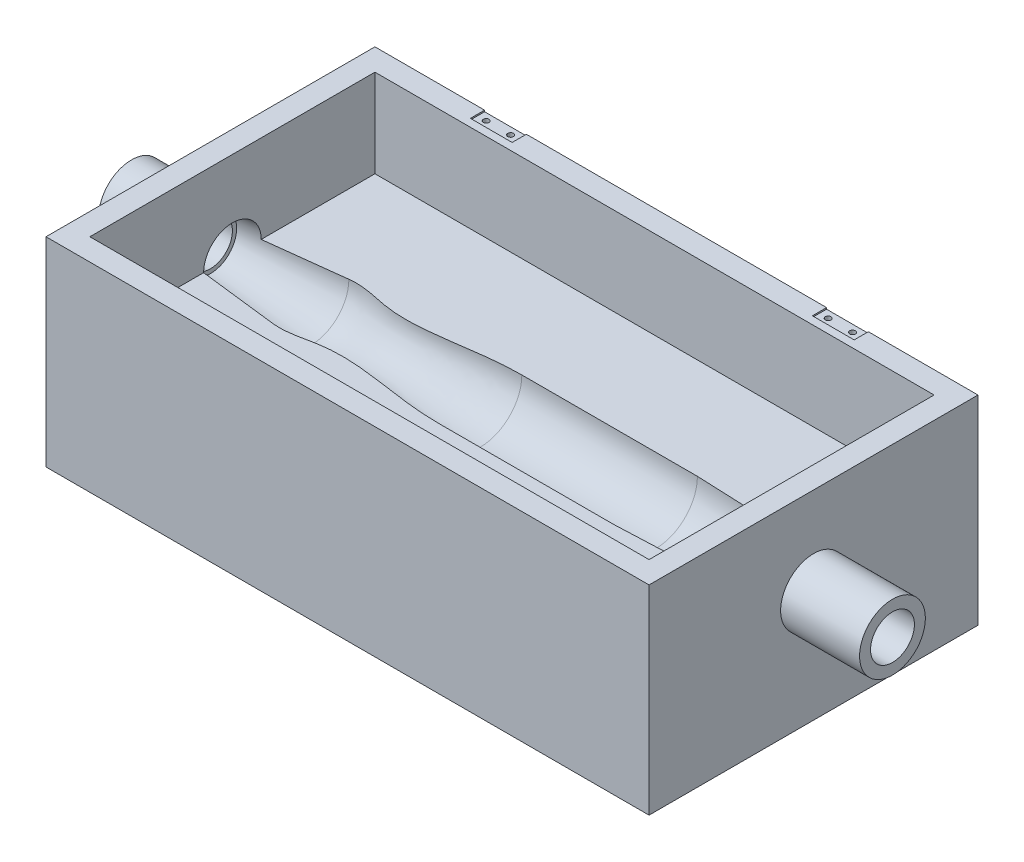
SolidWorks part; units mm, degrees
ref_plane "Front Plane" through (0, 0, 0) normal (0, 0, 1) x (1, 0, 0)
ref_plane "Top Plane" through (0, 0, 0) normal (0, 1, 0) x (1, 0, 0)
ref_plane "Right Plane" through (0, 0, 0) normal (1, 0, 0) x (0, 0, -1)
sketch "Sketch1" plane through (0, 0, 0) normal (0, 0, 1) x (1, 0, 0)
  line L0 (-137.5, 0) -> (137.5, 0)
  line L1 (-137.5, 11.938) -> (-137.5, 0)
  line L2 (-91.78, 17.399) -> (-91.78, 0) construction
  line L3 (-72.984, 15.24) -> (-72.984, 0) construction
  line L4 (-14.564, 19.05) -> (-14.564, 0) construction
  line L5 (-137.5, 11.938) -> (-91.78, 17.399)
  line L6 (119.602, 0) -> (119.602, 16.764) construction
  line L7 (65.5, 0) -> (65.5, 19.05) construction
  line L8 (65.5, 19.05) -> (119.602, 16.764)
  line L9 (-14.564, 19.05) -> (65.5, 19.05)
  line L10 (133.826, 14.351) -> (133.826, 0) construction
  line L11 (137.5, 0) -> (137.5, 7.747) construction
  line L12 (137.5, 7.747) -> (137.5, 0)
  spline S0 degree 3 poles (-91.78, 17.399) (-84.9013, 18.2206) (-60.5493, 10.0128) (-35.8294, 19.05) (-14.564, 19.05) knots 0 0 0 0 0.244238 1 1 1 1
  spline S1 degree 3 poles (119.602, 16.764) (126.4467, 16.4748) (132.2517, 15.7308) (137.5, 12.3228) (137.5, 7.747) knots 0 0 0 0 0.656248 1 1 1 1
  point P16 (0, 0)
  dimension "D2" = 45.72
  dimension "D3" = 11.938
  dimension "D1" = 16.764
  dimension "D4" = 64.516
  dimension "D5" = 15.24
  dimension "D6" = 19.05
  dimension "D7" = 122.936
  dimension "D8" = 203
  dimension "D9" = 19.05
  dimension "D10" = 54.102
  dimension "D11" = 275
  dimension "D12" = 14.351
  dimension "D13" = 7.747
  dimension "D14" = 14.224
  dimension "D15" = 17.399
sketch "Sketch2" plane through (0, 0, 0) normal (0, 0, 1) x (1, 0, 0)
  line L0 (-137.5, -50.8) -> (-137.5, 0)
  line L1 (-137.5, 0) -> (137.5, 0)
  line L2 (137.5, 0) -> (137.5, -50.8)
  line L3 (137.5, -50.8) -> (-137.5, -50.8)
  line L4 (-137.5, 0) -> (137.5, 0) construction
  dimension "D1" = 50.8
extrude "Boss-Extrude1" add sketch "Sketch2" along normal blind 75 and the other way blind 75
sketch "Sketch4" plane through (0, 0, 0) normal (0, 1, 0) x (1, 0, 0)
  line L0 (-137.5, 75) -> (137.5, 75)
  line L5 (-137.5, -75) -> (137.5, -75)
  line L6 (137.5, -75) -> (137.5, 75)
  line L7 (-137.5, 75) -> (-137.5, -75)
  line L8 (-137.5, 75) -> (-137.5, -75) construction
  line L11 (-127.5, 65) -> (127.5, 65)
  line L12 (127.5, -65) -> (127.5, 65)
  line L13 (-127.5, -65) -> (127.5, -65)
  line L14 (-127.5, 65) -> (-127.5, -65)
  dimension "D1" = 10
extrude "Boss-Extrude4" add sketch "Sketch4" along normal blind 40.132
revolve "Cut-Revolve1" cut sketch "Sketch1" angle 360 about L0
sketch "Sketch3" plane through (137.5, 0, 0) normal (1, 0, 0) x (0, 0, -1)
  circle A0 centre (0, 0) radius 10
  circle A1 centre (0, 0) radius 15
  dimension "D1" = 30
  dimension "D2" = 20
extrude "Boss-Extrude2" add sketch "Sketch3" along normal blind 36
mirror "Mirror1" about plane through (0, 0, 0) normal (1, 0, 0) of "Boss-Extrude2"
sketch "Sketch5" plane through (0, 40.132, 0) normal (0, 1, 0) x (1, 0, 0)
  line L0 (137.5, 75) -> (-137.5, 75) construction
  line L1 (-87.5, 75) -> (-68.45, 75)
  line L2 (-87.5, 75) -> (-87.5, 68.52)
  line L3 (-87.5, 68.52) -> (-68.45, 68.52)
  line L4 (-68.45, 75) -> (-68.45, 68.52)
  line L5 (-137.5, 75) -> (-137.5, -75) construction
  line L6 (68.45, 75) -> (87.5, 75)
  line L7 (68.45, 75) -> (68.45, 68.52)
  line L8 (68.45, 68.52) -> (87.5, 68.52)
  line L9 (87.5, 75) -> (87.5, 68.52)
  line L10 (137.5, -75) -> (137.5, 75) construction
  dimension "D1" = 19.05
  dimension "D2" = 6.48
  dimension "D3" = 50
  dimension "D4" = 50
extrude "Cut-Extrude1" cut sketch "Sketch5" against normal blind 0.64
hole_wizard "M2 Clearance Hole1" positions "Sketch6" profile "Sketch7" hole size "M2" standard "ANSI Metric"
sketch "Sketch6" plane through (0, 39.492, 0) normal (0, 1, 0) x (1, 0, 0)
  line L0 (-83.54, 71.76) -> (-72.41, 71.76) construction
  line L2 (72.41, 71.76) -> (83.54, 71.76) construction
  line L4 (68.45, 75) -> (68.45, 68.52) construction
  line L5 (87.5, 75) -> (68.45, 75) construction
  line L6 (-68.45, 75) -> (-87.5, 75) construction
  line L7 (-87.5, 75) -> (-87.5, 68.52) construction
  point P0 (-83.54, 71.76)
  point P2 (-72.41, 71.76)
  point P4 (72.41, 71.76)
  point P6 (83.54, 71.76)
  point P20 (68.45, 71.76)
  point P21 (77.975, 71.76)
  point P24 (77.975, 75)
  point P27 (-77.975, 75)
  point P28 (-77.975, 71.76)
  point P31 (-87.5, 71.76)
  dimension "D1" = 11.13
sketch "Sketch7" plane through (-83.54, 39.492, -71.76) normal (1, 0, 0) x (0, 0, 1)
  line L0 (0, 0) -> (0, 2.7811)
  line L1 (0, 2.7811) -> (1.3, 2)
  line L2 (1.3, 2) -> (1.3, 0)
  line L5 (1.3, 0) -> (0, 0)
  line L10 (0, 2.7811) -> (-1.3, 2) construction
  line L11 (0, -6.35) -> (0, 107.95) construction
  dimension "Hole Dia." = 2.6
  dimension "Hole Depth" = 2
  dimension "Drill Angle" = 118
